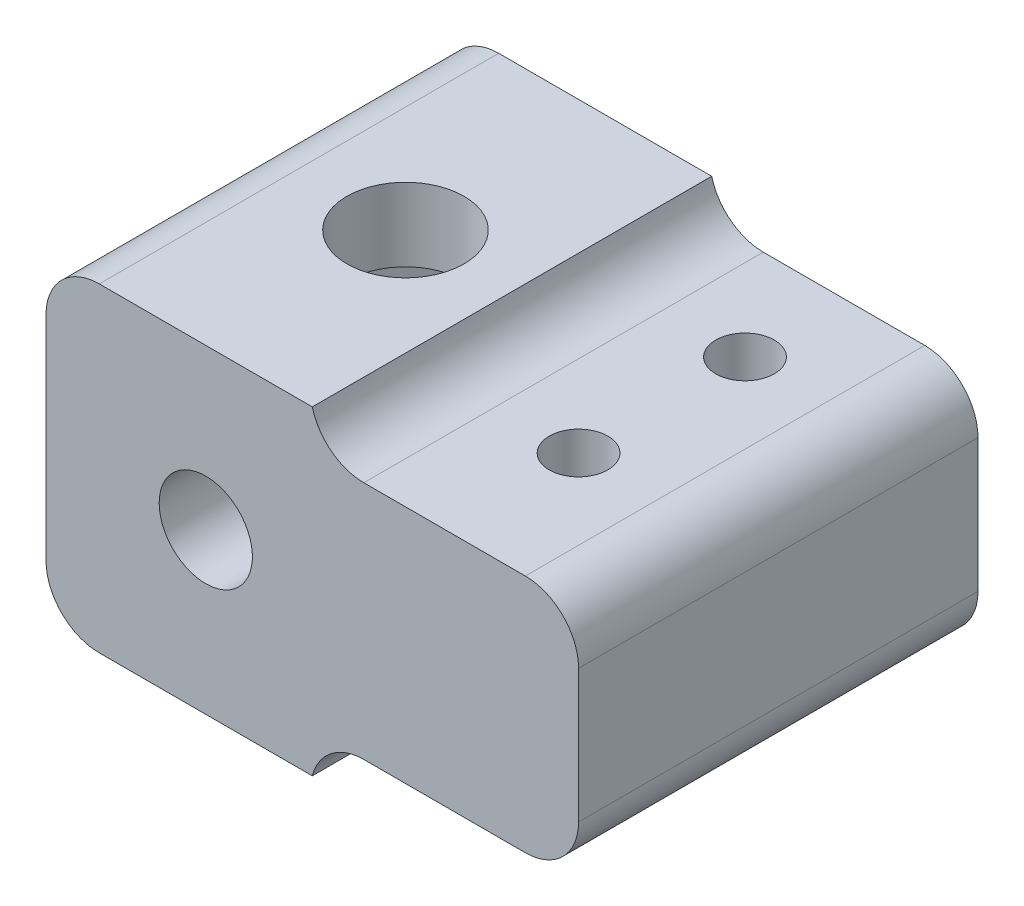
SolidWorks part; units mm, degrees
ref_plane "Front Plane" through (0, 0, 0) normal (0, 0, 1) x (1, 0, 0)
ref_plane "Top Plane" through (0, 0, 0) normal (0, 1, 0) x (1, 0, 0)
ref_plane "Right Plane" through (0, 0, 0) normal (1, 0, 0) x (0, 0, -1)
sketch "Sketch1" plane through (0, 0, 0) normal (0, 0, 1) x (1, 0, 0)
  circle A0 centre (0, 0) radius 1.25
  circle A1 centre (0, 0) radius 4.5
  dimension "D1" = 2.5
  dimension "D2" = 9
extrude "Boss-Extrude1" add sketch "Sketch1" along normal blind 8
sketch "Sketch2" plane through (0, 0, 0) normal (0, 0, -1) x (-1, 0, 0)
  circle A0 centre (0, 0) radius 1.25 construction
  circle A1 centre (0, 0) radius 4.5
  circle A2 centre (0, 0) radius 4.5
  circle A3 centre (0, 0) radius 1.25
  circle A4 centre (0, 0) radius 1.75
  circle M3 centre (0, 0) radius 1.25
  dimension "D2" = 3.5
  dimension "D1" = 0
extrude "Cut-Extrude1" cut sketch "Sketch2" against normal blind 4 contours A4 M3 region at (1.7005, 0, 0)
sketch "Sketch4" plane through (0, 0, 0) normal (0, 0, -1) x (-1, 0, 0)
  line L1 (3.25, -3.25) -> (-3.25, -3.25)
  line L2 (3.25, -3.25) -> (3.25, 3.25)
  line L3 (3.25, 3.25) -> (-3.25, 3.25)
  line L4 (-3.25, -3.25) -> (-3.25, 3.25)
  line L5 (0, 3.25) -> (0, -3.25) construction
  line L6 (3.25, 0) -> (-3.25, 0) construction
  line L7 (6, -6) -> (-6, -6)
  line L8 (6, -6) -> (6, 6)
  line L9 (6, 6) -> (-6, 6)
  line L10 (-6, -6) -> (-6, 6)
  line L11 (0, 6) -> (0, -6) construction
  line L12 (6, 0) -> (-6, 0) construction
  point P0 (0, 0)
  point P4 (0, 0)
  circle M5 centre (0, 0) radius 1.75
  circle M6 centre (0, 0) radius 4.5
  dimension "D1" = 6.5
  dimension "D2" = 6.5
  dimension "D3" = 12
  dimension "D4" = 12
extrude "Boss-Extrude2" add sketch "Sketch4" along normal blind 15
sketch "Sketch5" plane through (6, 0, 0) normal (1, 0, 0) x (0, 0, -1)
  line L4 (0, 6) -> (0, -6)
  line L5 (0, -6) -> (15, -6)
  line L6 (15, -6) -> (15, 6)
  line L7 (15, 6) -> (0, 6)
  line L8 (0, 6) -> (0, -6)
  line L9 (0, -6) -> (15, -6)
  line L10 (15, -6) -> (15, 6)
  line L11 (15, 6) -> (0, 6)
  dimension "D1" = 0
extrude "Boss-Extrude3" add sketch "Sketch5" along normal blind 8
sketch "Sketch6" plane through (0, 6, 0) normal (0, 1, 0) x (1, 0, 0)
  line L0 (4, 15) -> (4, 0) construction
  line L1 (4, 0) -> (14, 15) construction
  line L2 (9, 7.5) -> (9, 15) construction
  line L3 (9, 15) -> (9, 0) construction
  line L4 (-6, 0) -> (14, 0)
  line L5 (14, 0) -> (14, 15)
  line L6 (14, 15) -> (-6, 15)
  line L7 (-6, 15) -> (-6, 0)
  line L8 (-6, 0) -> (14, 0)
  line L9 (14, 0) -> (14, 15)
  line L10 (14, 15) -> (-6, 15)
  line L11 (-6, 15) -> (-6, 0)
  circle A0 centre (9, 11.25) radius 1.1
  circle A1 centre (9, 5) radius 1.1
  dimension "D2" = 2.2
  dimension "D3" = 2.2
  dimension "D4" = 5
  dimension "D1" = 0
extrude "Cut-Extrude2" cut sketch "Sketch6" against normal through all both and the other way through all contours A0 | A1
fillet "Fillet1" radius 2 2 edges at (-6, 6, -7.5) (-6, -6, -7.5)
sketch "Sketch7" plane through (0, -6, 0) normal (0, -1, 0) x (1, 0, 0)
  line L0 (14, -15) -> (-4, -15) construction
  line L1 (14, 0) -> (4, 0)
  line L2 (14, 0) -> (14, -15)
  line L3 (14, -15) -> (4, -15)
  line L4 (4, 0) -> (4, -15)
  line L5 (9, -5) -> (9, 0) construction
  circle A0 centre (9, -5) radius 1.1 construction
  circle A1 centre (9, -5) radius 1.1
  dimension "D1" = 5
extrude "Cut-Extrude3" cut sketch "Sketch7" against normal blind 1.5
extrude "Cut-Extrude4" cut sketch "Sketch7<2>" along normal blind 1.5 from surface starting at face at (9, 6, -12.35)
sketch "Sketch7<2>" plane through (0, -6, 0) normal (0, -1, 0) x (1, 0, 0) same geometry as "Sketch7"
fillet "Fillet2" radius 2 4 edges at (14, -4.5, -7.5) (14, 4.5, -7.5) (4, 4.5, -7.5) (4, -4.5, -7.5)
extrude "Cut-Extrude5" cut sketch "Sketch1<2>" against normal blind 8 from surface starting at face at (4.5, 0, 8)
sketch "Sketch1<2>" plane through (0, 0, 0) normal (0, 0, 1) x (1, 0, 0) same geometry as "Sketch1"
extrude "Boss-Extrude5" add sketch "Sketch4<4>" along normal blind 3 contours L4 L1 L2 L3 M6 M5 | L4 L1 M6 | L4 L3 M6 | L2 L3 M6 | L1 L2 M6 region at (-3.2045, -3.2045, 0) region at (0, -3.1581, 0) region at (3.2045, -3.2045, 0) region at (-3.2045, 3.2045, 0) region at (3.2045, 3.2045, 0)
sketch "Sketch4<4>" plane through (0, 0, 0) normal (0, 0, -1) x (-1, 0, 0) same geometry as "Sketch4"
sketch "Sketch8" plane through (0, -6, 0) normal (0, -1, 0) x (1, 0, 0)
  line L0 (-4, 0) -> (4, -15) construction
  circle A0 centre (0, -7.5) radius 2.2
  dimension "D1" = 4.4
extrude "Cut-Extrude6" cut sketch "Sketch8" against normal blind 14
